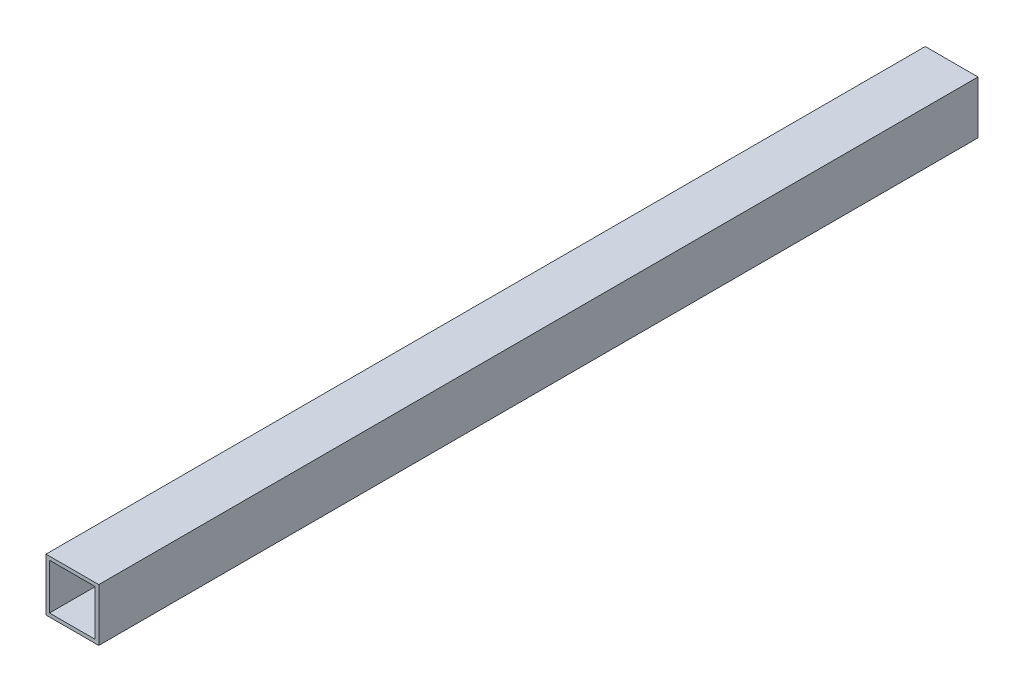
SolidWorks part; units mm, degrees
ref_plane "Front Plane" through (0, 0, 0) normal (0, 0, 1) x (1, 0, 0)
ref_plane "Top Plane" through (0, 0, 0) normal (0, 1, 0) x (1, 0, 0)
ref_plane "Right Plane" through (0, 0, 0) normal (1, 0, 0) x (0, 0, -1)
sketch "Sketch3" plane through (0, 0, 0) normal (0, 0, 1) x (1, 0, 0)
  line L1 (0, 0) -> (15, 0)
  line L2 (0, 0) -> (0, 15)
  line L3 (0, 15) -> (15, 15)
  line L4 (15, 0) -> (15, 15)
  dimension "D1" = 15
extrude "Extrude-Thin1" add sketch "Sketch3" along normal blind 250 thin thin type one direction reverse wall 1
